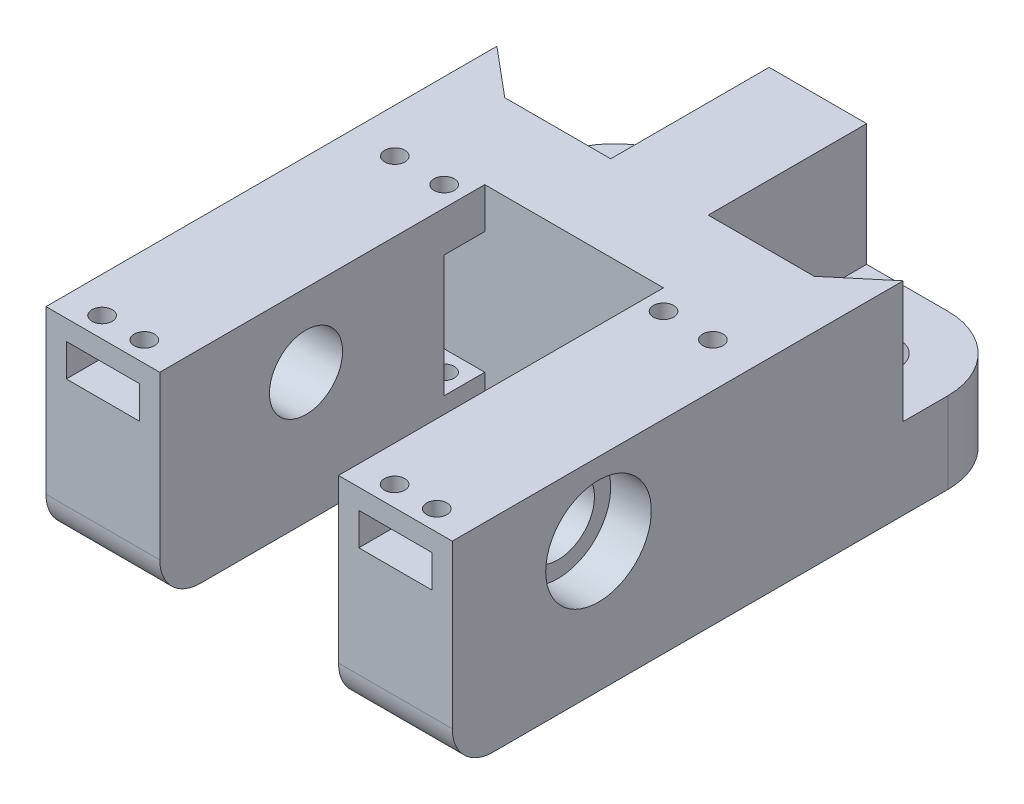
SolidWorks part; units mm, degrees
ref_plane "정면" through (0, 0, 0) normal (0, 0, 1) x (1, 0, 0)
ref_plane "윗면" through (0, 0, 0) normal (0, 1, 0) x (1, 0, 0)
ref_plane "우측면" through (0, 0, 0) normal (1, 0, 0) x (0, 0, -1)
sketch "스케치1" plane through (0, 0, 0) normal (0, 0, 1) x (1, 0, 0)
  line L1 (-25, -12.5) -> (25, -12.5)
  line L2 (-25, -12.5) -> (-25, 12.5)
  line L3 (-25, 12.5) -> (25, 12.5)
  line L4 (25, -12.5) -> (25, 12.5)
  line L5 (-25, -12.5) -> (25, 12.5) construction
  line L6 (-25, 12.5) -> (25, -12.5) construction
  point P0 (0, 0)
  point P6 (0, 0)
  dimension "D1" = 50
  dimension "D2" = 25
extrude "보스-돌출1" add sketch "스케치1" along normal blind 70
sketch "스케치2" plane through (0, 0, 70) normal (0, 0, 1) x (1, 0, 0)
  line L0 (-25, -12.5) -> (25, -12.5) construction
  line L1 (-11, -12.5) -> (11, -12.5)
  line L2 (-11, -12.5) -> (-11, 12.5)
  line L3 (-11, 12.5) -> (11, 12.5)
  line L4 (11, -12.5) -> (11, 12.5)
  line L5 (25, 12.5) -> (-25, 12.5) construction
  line L7 (0, -13.75) -> (0, 13.75) construction
  point P12 (0, -12.5)
  dimension "D1" = 22
extrude "컷-돌출1" cut sketch "스케치2" against normal blind 40
sketch "스케치3" plane through (25, 0, 0) normal (1, 0, 0) x (0, 0, -1)
  line L0 (-70, -12.5) -> (-70, 12.5) construction
  line L1 (-70, 0) -> (-16.1635, 0) construction
  line L2 (-30, -12.5) -> (-30, 12.5) construction
  line L3 (-30, -12.5) -> (-30, 12.5) construction
  line L4 (-70, 12.5) -> (0, 12.5) construction
  circle A0 centre (-52, 3.5) radius 4.5
  dimension "D1" = 9
  dimension "D2" = 22
  dimension "D3" = 9
extrude "컷-돌출2" cut sketch "스케치3" against normal blind 50
sketch "스케치4" plane through (25, 0, 0) normal (-1, 0, 0) x (0, 0, 1)
  circle A0 centre (52, 3.5) radius 6.5
  dimension "D1" = 13
extrude "컷-돌출4" cut sketch "스케치4" along normal blind 5 contours A0
sketch "스케치5" plane through (0, 12.5, 0) normal (0, 1, 0) x (1, 0, 0)
  line L0 (16, -9) -> (56.6647, -9) construction
  line L1 (16, -9) -> (16, 25.2953) construction
  line L2 (25, -70) -> (25, 0) construction
  line L3 (25, 0) -> (-25, 0) construction
  line L4 (16, 12.3557) -> (16, 0)
  line L5 (25, -9) -> (37.3557, -9)
  circle A0 centre (16, -9) radius 3
  arc A1 (25, -9) -> (16, 0) centre (16, -9) ccw
  arc A2 (37.3557, -9) -> (16, 12.3557) centre (16, -9) ccw
  dimension "D1" = 6
  dimension "D2" = 9
  dimension "D3" = 9
extrude "컷-돌출5" cut sketch "스케치5" against normal blind 29
mirror "대칭 복사2" about plane through (0, 0, 0) normal (1, 0, 0) of "컷-돌출5", "컷-돌출4"
ref_point "점1"
ref_point "점2"
ref_axis "기준축1" through (36.6861, 12.5, 9) along (-1, 0, 0)
sketch "스케치6" plane through (0, 12.5, 0) normal (0, 1, 0) x (1, 0, 0)
  line L0 (25, -70) -> (25, -9) construction
  line L2 (6, -19.5) -> (6, 5.2581)
  line L3 (25, -14.5022) -> (25, 5.2581)
  line L4 (25, 5.2581) -> (6, 5.2581)
  line L7 (19.0438, -19.5) -> (6, -19.5)
  line L9 (36.6861, -9) -> (-17.6842, -9) construction
  line L10 (19.0438, -19.5) -> (25, -14.5022)
  line L11 (16, -9) -> (6, -17.391) construction
  line L12 (-25, -14.5022) -> (-25, 5.2581)
  line L14 (0, -24.5) -> (0, 0) construction
  line L15 (-6, -19.5) -> (-6, 5.2581)
  line L16 (-19.0438, -19.5) -> (-6, -19.5)
  line L17 (-19.0438, -19.5) -> (-25, -14.5022)
  line L18 (-6, 5.2581) -> (-25, 5.2581)
  dimension "D1" = 10.5
  dimension "D2" = 10
  dimension "D3" = 40
  dimension "D4" = 10
extrude "컷-돌출6" cut sketch "스케치6" against normal blind 15 and the other way blind 5
sketch "스케치7" plane through (-11, 0, 0) normal (1, 0, 0) x (0, 0, -1)
  line L0 (-30, 0) -> (-41.4091, 0) construction
  line L1 (-30, 12.5) -> (-30, -12.5) construction
  line L2 (-30, -7.5) -> (-35, -7.5)
  line L3 (-30, 7.5) -> (-35, 7.5)
  line L4 (-30, 7.5) -> (-30, -7.5)
  line L6 (-35, 7.5) -> (-35, -7.5)
  line L7 (-30, 12.5) -> (-70, 12.5) construction
  point P9 (-33.7321, 0)
  point P10 (-30, 0.2785)
  point P12 (-35, 0)
  dimension "D1" = 5
  dimension "D2" = 5
extrude "컷-돌출7" cut sketch "스케치7" against normal blind 10
sketch "스케치8" plane through (0, -7.5, 0) normal (0, 1, 0) x (1, 0, 0)
  line L0 (-16.5374, -35) -> (-16.5374, -30) construction
  line L3 (-11, -35) -> (-11, -30) construction
  circle A0 centre (-13.5, -32.5) radius 1.25
  circle A1 centre (-19.5748, -32.5) radius 1.25
  point P2 (0, 0)
  point P8 (-12.6558, -32.5)
  point P9 (-13.4424, -32.5)
  point P14 (0, 0)
  dimension "D1" = 2.5
  dimension "D2" = 2.5
extrude "컷-돌출8" cut sketch "스케치8" against normal blind 10 and the other way blind 30 contours A1 | A0 region at (-13.5, -7.5, 32.5) region at (-19.5748, -7.5, 32.5)
sketch "스케치9" plane through (0, -12.5, 0) normal (0, -1, 0) x (1, 0, 0)
  circle A0 centre (-19.5748, 32.5) radius 2.75
  circle A1 centre (-13.5, 32.5) radius 2.75
  dimension "D1" = 5.5
extrude "컷-돌출9" cut sketch "스케치9" against normal blind 3
fillet "필렛2" radius 5 2 edges at (18, -12.5, 70) (-18, -12.5, 70)
sketch "스케치10" plane through (0, 0, 70) normal (0, 0, 1) x (1, 0, 0)
  line L0 (-18, 12.5) -> (-18, -2.0242) construction
  line L1 (-11, 12.5) -> (-25, 12.5) construction
  line L3 (-22.5, 10.0362) -> (-13.5, 10.0362)
  line L4 (-22.5, 10.0362) -> (-22.5, 6.0362)
  line L5 (-22.5, 6.0362) -> (-13.5, 6.0362)
  line L6 (-13.5, 10.0362) -> (-13.5, 6.0362)
  point P8 (-18, 10.0362)
  dimension "D1" = 9
  dimension "D2" = 4
extrude "컷-돌출10" cut sketch "스케치10" against normal blind 5
sketch "스케치12" plane through (0, 10.0362, 0) normal (0, -1, 0) x (1, 0, 0)
  line L0 (-18, 70) -> (-18, 65) construction
  line L1 (-13.5, 70) -> (-22.5, 70) construction
  line L2 (-13.5, 65) -> (-22.5, 65) construction
  line L3 (-13.5, 67.5) -> (-18, 67.5) construction
  line L4 (-13.5, 65) -> (-13.5, 70) construction
  circle A0 centre (-15.4008, 67.5) radius 1.25
  circle A1 centre (-20.5992, 67.5) radius 1.25
  point P8 (-15.4008, 67.5)
  dimension "D1" = 2.5
extrude "컷-돌출11" cut sketch "스케치12" against normal blind 10
mirror "대칭 복사3" about plane through (0, 0, 0) normal (1, 0, 0) of "컷-돌출10", "컷-돌출11", "컷-돌출8", "컷-돌출7", "컷-돌출9"
